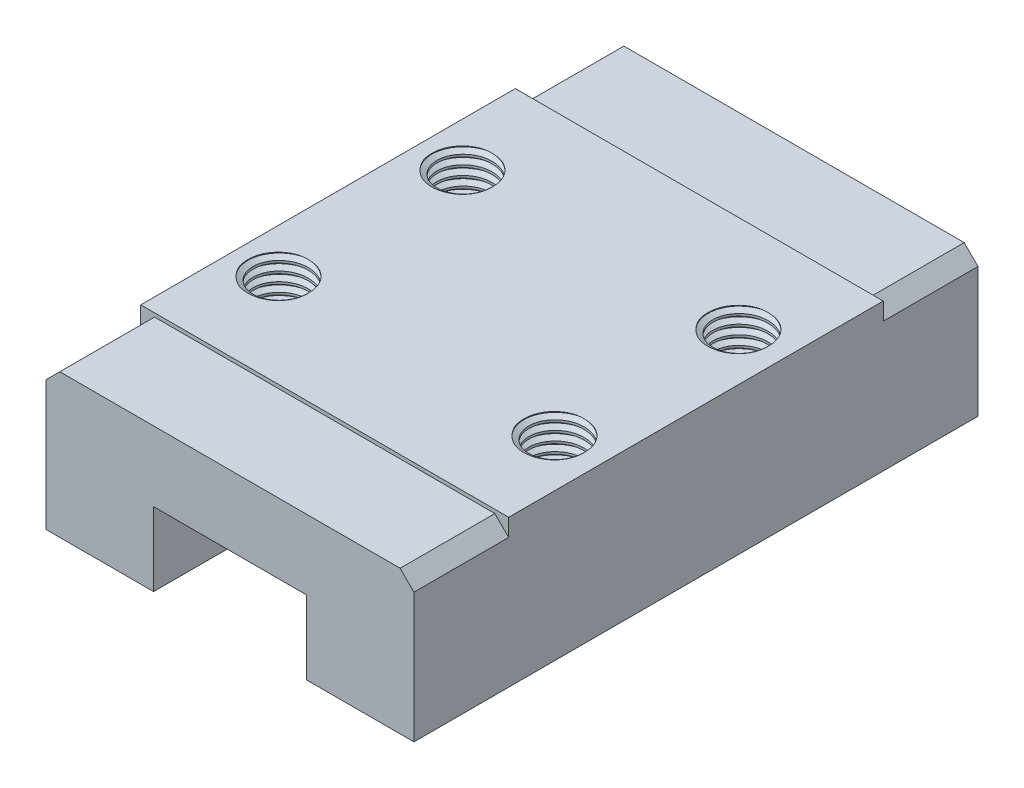
SolidWorks part; units mm, degrees
ref_plane "Front Plane" through (0, 0, 0) normal (0, 0, 1) x (1, 0, 0)
ref_plane "Top Plane" through (0, 0, 0) normal (0, 1, 0) x (1, 0, 0)
ref_plane "Right Plane" through (0, 0, 0) normal (1, 0, 0) x (0, 0, -1)
sketch "Sketch1" plane through (0, 0, 0) normal (0, 0, 1) x (1, 0, 0)
  line L0 (-10, 0) -> (10, 0)
  line L1 (10, 0) -> (10, -8)
  line L2 (10, -8) -> (4.15, -8)
  line L3 (4.15, -8) -> (4.15, -4)
  line L4 (4.15, -4) -> (-4.15, -4)
  line L5 (-4.15, -4) -> (-4.15, -8)
  line L6 (-4.15, -8) -> (-10, -8)
  line L7 (-10, -8) -> (-10, 0)
  dimension "D1" = 20
  dimension "D2" = 8
  dimension "D3" = 8.3
  dimension "D4" = 4
extrude "Boss-Extrude1" add sketch "Sketch1" along normal blind 30.66
sketch "Sketch2" plane through (0, 0, 0) normal (0, 1, 0) x (1, 0, 0)
  line L0 (-10, -30.66) -> (-10, 0) construction
  circle A0 centre (-7.5, -10.33) radius 1.5
  circle A1 centre (7.5, -10.33) radius 1.5
  circle A2 centre (7.5, -20.33) radius 1.5
  circle A3 centre (-7.5, -20.33) radius 1.5
  point P10 (-10, -15.33)
  dimension "D1" = 3
  dimension "D2" = 15
  dimension "D3" = 10
  dimension "D4" = 5
  dimension "D5" = 7.5
extrude "Cut-Extrude1" cut sketch "Sketch2" against normal blind 6
sketch "Sketch3" plane through (0, 0, 30.66) normal (0, 0, 1) x (1, 0, 0)
  line L0 (10, 0) -> (-10, 0) construction
  line L1 (10, 0) -> (-10, 0)
  line L2 (-10, 0) -> (-10, -0.2)
  line L3 (-10, 0) -> (-10, -8) construction
  line L4 (-10, -0.2) -> (10, -0.2)
  line L5 (10, -8) -> (10, 0) construction
  line L6 (10, -0.2) -> (10, 0)
  dimension "D1" = 0.2
extrude "Cut-Extrude2" cut sketch "Sketch3" against normal blind 5.15
sketch "Sketch4" plane through (0, 0, 0) normal (0, 0, -1) x (-1, 0, 0)
  line L0 (10, 0) -> (10, -8) construction
  line L1 (-10, 0) -> (10, 0)
  line L2 (-10, 0) -> (-10, -0.2)
  line L3 (-10, -0.2) -> (10, -0.2)
  line L4 (10, 0) -> (10, -0.2)
  dimension "D1" = 0.2
extrude "Cut-Extrude3" cut sketch "Sketch4" against normal blind 5.15
chamfer "Chamfer1" distance 0.75 angle 45 4 edges at (10, -0.2, 28.085) (-10, -0.2, 28.085) (-10, -0.2, 2.575) (10, -0.2, 2.575)
thread "Thread1" pitch 0.5 start angle 0, offset 0, length 0, pitch 0.5, diameter 3
ref_plane "Plane1" through (9, -6, 10.33) normal (0, 0, 1) x (1, 0, 0)
sketch "Thread Profile1" plane through (9, -6, 10.33) normal (0, 0, 1) x (1, 0, 0)
  line L0 (0, 0) -> (0, 0.5) construction
  line L1 (0, 0) -> (0.2706, 0.1562)
  line L2 (0.2706, 0.1562) -> (0.2706, 0.2187)
  line L3 (0.2706, 0.2187) -> (0, 0.375)
  line L4 (0.2706, 0.1875) -> (0, 0.1875) construction
  line L11 (0, 0) -> (0, 0.375)
  point P2 (0, 0)
  dimension "Pitch" = 0.5
  dimension "Profile_Angle" = 60
  dimension "Profile_Land" = 0.0625
  dimension "Profile_Height" = 0.2706
thread "Thread2" pitch 0.5 profile "Thread Profile2" start angle 0, offset 0, length 0, pitch 0.5, diameter 3
ref_plane "Plane2" through (9, -6, 20.33) normal (0, 0, 1) x (1, 0, 0)
sketch "Thread Profile2" plane through (9, -6, 20.33) normal (0, 0, 1) x (1, 0, 0)
  line L0 (0, 0) -> (0, 0.5) construction
  line L1 (0, 0) -> (0.2706, 0.1562)
  line L2 (0.2706, 0.1562) -> (0.2706, 0.2187)
  line L3 (0.2706, 0.2187) -> (0, 0.375)
  line L4 (0.2706, 0.1875) -> (0, 0.1875) construction
  line L11 (0, 0) -> (0, 0.375)
  point P2 (0, 0)
  dimension "Pitch" = 0.5
  dimension "Profile_Angle" = 60
  dimension "Profile_Land" = 0.0625
  dimension "Profile_Height" = 0.2706
thread "Thread3" pitch 0.5 profile "Thread Profile3" start angle 0, offset 0, length 0, pitch 0.5, diameter 3
ref_plane "Plane3" through (-6, -6, 10.33) normal (0, 0, 1) x (1, 0, 0)
sketch "Thread Profile3" plane through (-6, -6, 10.33) normal (0, 0, 1) x (1, 0, 0)
  line L0 (0, 0) -> (0, 0.5) construction
  line L1 (0, 0) -> (0.2706, 0.1562)
  line L2 (0.2706, 0.1562) -> (0.2706, 0.2187)
  line L3 (0.2706, 0.2187) -> (0, 0.375)
  line L4 (0.2706, 0.1875) -> (0, 0.1875) construction
  line L11 (0, 0) -> (0, 0.375)
  point P2 (0, 0)
  dimension "Pitch" = 0.5
  dimension "Profile_Angle" = 60
  dimension "Profile_Land" = 0.0625
  dimension "Profile_Height" = 0.2706
thread "Thread4" pitch 0.5 profile "Thread Profile4" start angle 0, offset 0, length 0, pitch 0.5, diameter 3
ref_plane "Plane4" through (-6, -6, 20.33) normal (0, 0, 1) x (1, 0, 0)
sketch "Thread Profile4" plane through (-6, -6, 20.33) normal (0, 0, 1) x (1, 0, 0)
  line L0 (0, 0) -> (0, 0.5) construction
  line L1 (0, 0) -> (0.2706, 0.1562)
  line L2 (0.2706, 0.1562) -> (0.2706, 0.2187)
  line L3 (0.2706, 0.2187) -> (0, 0.375)
  line L4 (0.2706, 0.1875) -> (0, 0.1875) construction
  line L11 (0, 0) -> (0, 0.375)
  point P2 (0, 0)
  dimension "Pitch" = 0.5
  dimension "Profile_Angle" = 60
  dimension "Profile_Land" = 0.0625
  dimension "Profile_Height" = 0.2706
equation "\"D4@Sketch2\"=\"D3@Sketch2\"/2"
equation "\"D5@Sketch2\"=\"D2@Sketch2\"/2"
